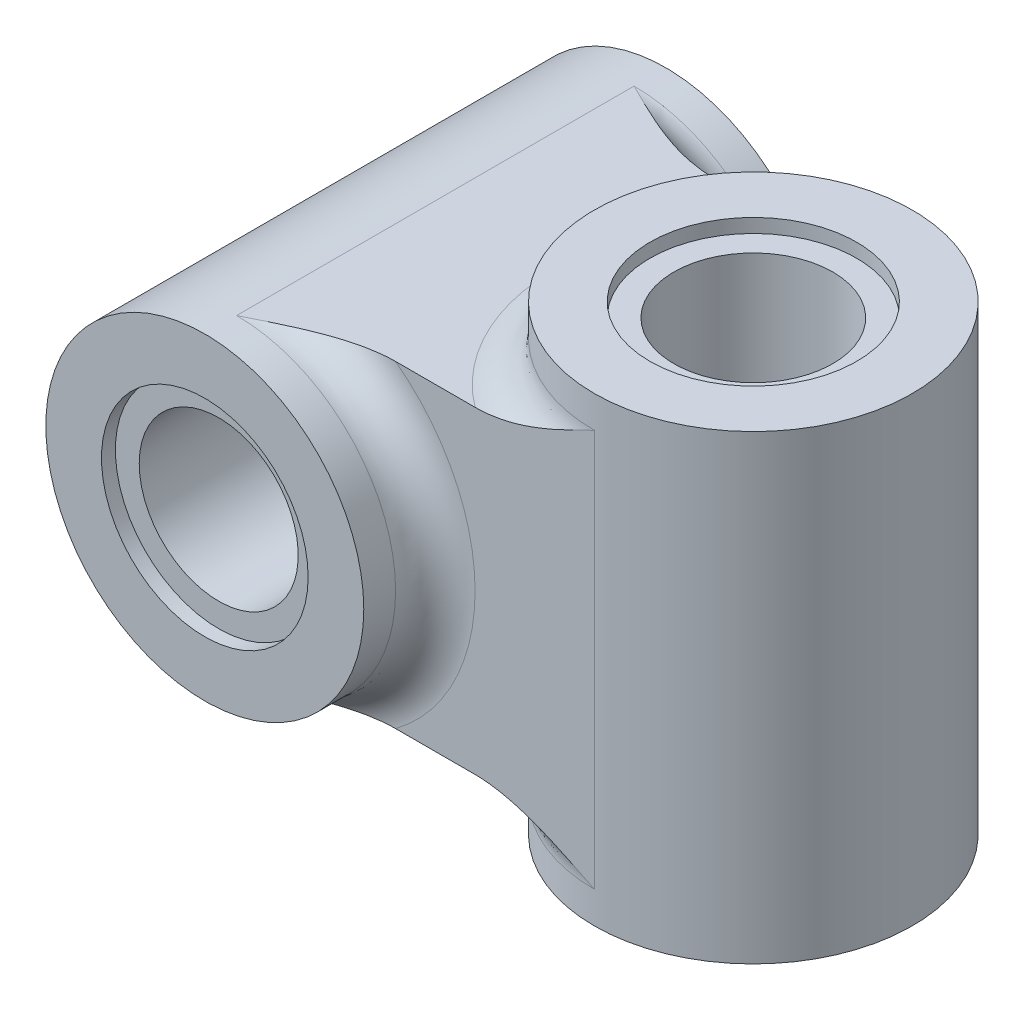
SolidWorks part; units mm, degrees
ref_plane "前视基准面" through (0, 0, 0) normal (0, 0, 1) x (1, 0, 0)
ref_plane "上视基准面" through (0, 0, 0) normal (0, 1, 0) x (1, 0, 0)
ref_plane "右视基准面" through (0, 0, 0) normal (1, 0, 0) x (0, 0, -1)
other "Configuration Table"
sketch "草图1" plane through (0, 0, 0) normal (0, 0, 1) x (1, 0, 0)
  circle A0 centre (0, 0) radius 20
  circle A1 centre (0, 0) radius 10
  dimension "D1" = 40
  dimension "D2" = 20
extrude "凸台-拉伸1" add sketch "草图1" along normal blind 58
sketch "草图2" plane through (0, 0, 0) normal (0, 1, 0) x (1, 0, 0)
  line L0 (-7.0354, -29) -> (29.939, -29) construction
  line L3 (20, 0) -> (-20, 0) construction
  line L4 (-20, -58) -> (20, -58) construction
  circle A2 centre (40, -29) radius 20
  circle A3 centre (40, -29) radius 10
  dimension "D1" = 40
  dimension "D2" = 20
  dimension "D3" = 40
extrude "凸台-拉伸2" add sketch "草图2" along normal mid plane 58 separate body contours A3 | A2 region at (40, 0, 29)
sketch "草图3" plane through (0, 0, 0) normal (1, 0, 0) x (0, 0, -1)
  line L0 (-58, -20) -> (0, -20) construction
  line L5 (-49, -20) -> (-9, -20)
  line L6 (-49, -20) -> (-49, 20)
  line L7 (-49, 20) -> (-9, 20)
  line L8 (-9, -20) -> (-9, 20)
  line L9 (0, 20) -> (-58, 20) construction
  line L10 (-9, -29) -> (-9, 29) construction
  line L11 (-49, 29) -> (-49, -29) construction
extrude "凸台-拉伸3" add sketch "草图3" along normal blind 40 contours L7 L8 L5 L6
sketch "草图5" plane through (0, 29, 0) normal (0, 1, 0) x (1, 0, 0)
  circle A0 centre (40, -29) radius 10 construction
  circle A1 centre (40, -29) radius 10
extrude "切除-拉伸1" cut sketch "草图5" against normal blind 118
sketch "草图6" plane through (0, 0, 0) normal (0, 0, -1) x (-1, 0, 0)
  circle A0 centre (0, 0) radius 10 construction
  circle A1 centre (0, 0) radius 10
extrude "切除-拉伸2" cut sketch "草图6" against normal blind 118
fillet "圆角1" radius 5 4 edges at (20, -20, 29) (20, 0, 9) (20, 20, 29) (20, 0, 49)
sketch "草图7" plane through (0, 0, 0) normal (0, 0, -1) x (-1, 0, 0)
  circle A0 centre (0, 0) radius 13
  dimension "D1" = 26
extrude "切除-拉伸3" cut sketch "草图7" against normal blind 1.75
sketch "草图8" plane through (0, 0, 58) normal (0, 0, 1) x (1, 0, 0)
  circle A0 centre (0, 0) radius 13
  dimension "D1" = 26
extrude "切除-拉伸4" cut sketch "草图8" against normal blind 1.75
sketch "草图9" plane through (0, 29, 0) normal (0, 1, 0) x (1, 0, 0)
  circle A0 centre (40, -29) radius 13
  dimension "D1" = 26
extrude "切除-拉伸5" cut sketch "草图9" against normal blind 1.75
sketch "草图10" plane through (0, -29, 0) normal (0, -1, 0) x (1, 0, 0)
  circle A0 centre (40, 29) radius 13
  dimension "D1" = 26
extrude "切除-拉伸6" cut sketch "草图10" against normal blind 1.75
